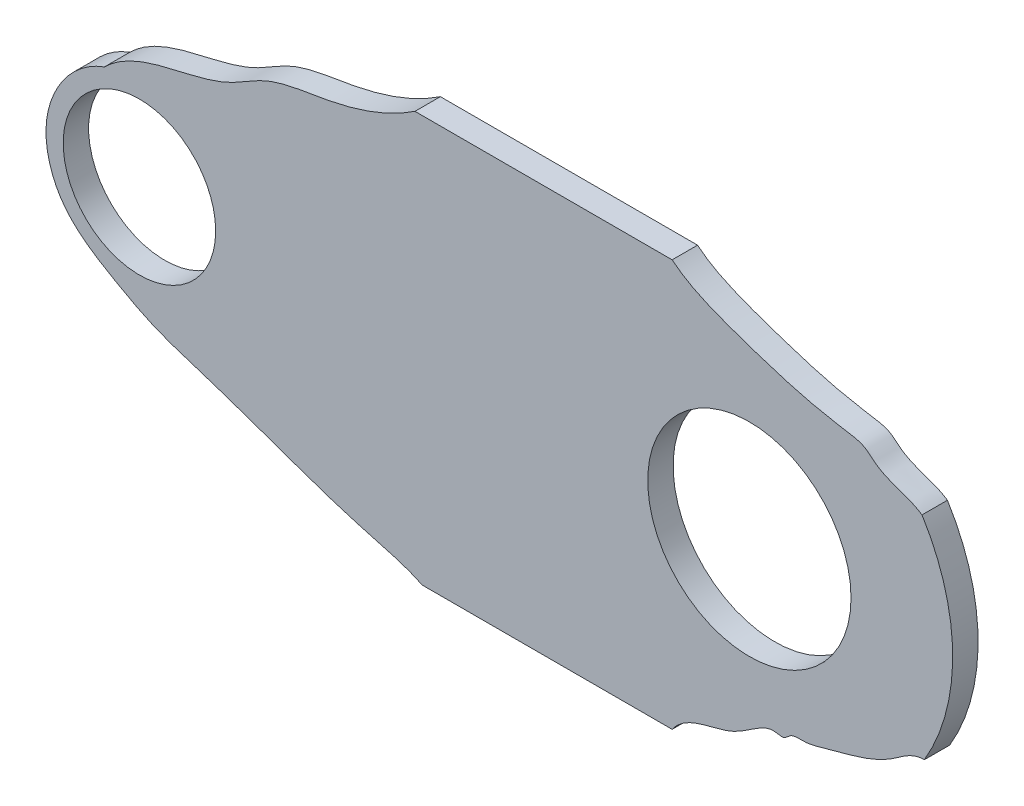
SolidWorks part; units mm, degrees
material "6061-T6 (SS)"
ref_plane "Front Plane" through (0, 0, 0) normal (0, 0, 1) x (1, 0, 0)
ref_plane "Top Plane" through (0, 0, 0) normal (0, 1, 0) x (1, 0, 0)
ref_plane "Right Plane" through (0, 0, 0) normal (1, 0, 0) x (0, 0, -1)
sketch "Sketch1" plane through (0, 0, 0) normal (0, 0, 1) x (1, 0, 0)
  line L0 (0, 0) -> (76.2, 0)
  line L1 (0, -50.8) -> (76.2, -50.8)
  arc A0 (0, 0) -> (0, -50.8) centre (0, -25.4) ccw
  arc A1 (76.2, -50.8) -> (76.2, 0) centre (76.2, -25.4) ccw
  circle A2 centre (0, -25.4) radius 9.525
  circle A3 centre (76.2, -25.4) radius 12.7
  dimension "D3" = 50.8
  dimension "D2" = 19.05
  dimension "D4" = 25.4
extrude "Boss-Extrude1" add sketch "Sketch1" along normal mid plane 3.175
sketch "Sketch2" plane through (0, 0, 1.5875) normal (0, 0, 1) x (1, 0, 0)
  line L0 (76.2, 0) -> (0, 0) construction
  line L1 (0, -50.8) -> (76.2, -50.8) construction
  line L2 (34.421, 0) -> (0, 0)
  line L3 (35.3528, -50.8) -> (0, -50.8)
  line L4 (66.5515, 0) -> (76.2, 0)
  line L5 (66.5515, -50.8) -> (76.2, -50.8)
  arc A0 (76.2, -50.8) -> (76.2, 0) centre (76.2, -25.4) ccw construction
  arc A1 (0, 0) -> (0, -50.8) centre (0, -25.4) ccw
  arc A3 (76.2, 0) -> (97.77, -11.9876) centre (76.2, -25.4) cw
  arc A4 (76.2, -50.8) -> (98.0566, -38.3402) centre (76.2, -25.4) ccw
  spline S0 degree 3 poles (34.421, 0) (31.1068, -2.238) (24.7837, -4.3916) (16.3726, -5.1676) (8.0871, -11.0509) (-0.0219, -10.2876) (-4.3758, -14.592) knots 0 0 0 0 0.285025 0.477252 0.592182 1 1 1 1
  spline S1 degree 3 poles (-4.3758, -14.592) (-8.4885, -16.0672) (-13.1576, -22.7674) (-10.0792, -32.9254) (-3.7775, -36.6878) (1.9661, -39.8241) (9.0494, -41.9679) (17.6036, -44.9974) (26.8294, -48.2819) (32.8571, -49.6068) (35.3528, -50.8) knots 0 0 0 0 0.186565 0.294462 0.418873 0.489089 0.577914 0.735962 0.881002 1 1 1 1
  spline S2 degree 3 poles (66.5515, -50.8) (68.3851, -48.2067) (72.799, -48.4343) (76.652, -45.6695) (78.8215, -44.3415) (80.5475, -44.9271) (81.4613, -43.7424) (83.3052, -44.0107) (85.9905, -43.1695) (89.7403, -42.2796) (94.0484, -40.5987) (96.4612, -38.3131) (98.0566, -38.3402) knots 0 0 0 0 0.243553 0.339654 0.417853 0.450838 0.478711 0.531667 0.597471 0.726484 0.867337 1 1 1 1
  spline S3 degree 3 poles (66.5515, 0) (68.219, -1.3842) (71.7164, -2.9804) (77.3466, -4.9234) (82.628, -6.5817) (87.2573, -7.5069) (90.453, -7.9306) (93.0568, -10.514) (95.9891, -10.7828) (97.77, -11.9876) knots 0 0 0 0 0.191375 0.338945 0.531515 0.680444 0.766415 0.804102 1 1 1 1
extrude "Cut-Extrude1" cut sketch "Sketch2" against normal up to next contours A1 L3 S1 S0 L2 | A3 S3 L4 | A4 S2 L5
equation "\"Width\"= 2"
equation "\"CenterSpacing\"= 3.000in"
equation "\"T\"= 0.1250in"
equation "\"BracketHole\"= 0.750in"
equation "\"OtherHole\"= 1.000in"
equation "\"Length\"= \"CenterSpacing\" + \"Width\""
equation "\"EndOffset\"= \"Width\" / 2"
equation "\"D3@Sketch1\"=\"Width\""
equation "\"D1@Sketch1\"=\"CenterSpacing\""
equation "\"D2@Sketch1\"=\"BracketHole\""
equation "\"D4@Sketch1\"=\"OtherHole\""
equation "\"D1@Boss-Extrude1\"=\"T\""
